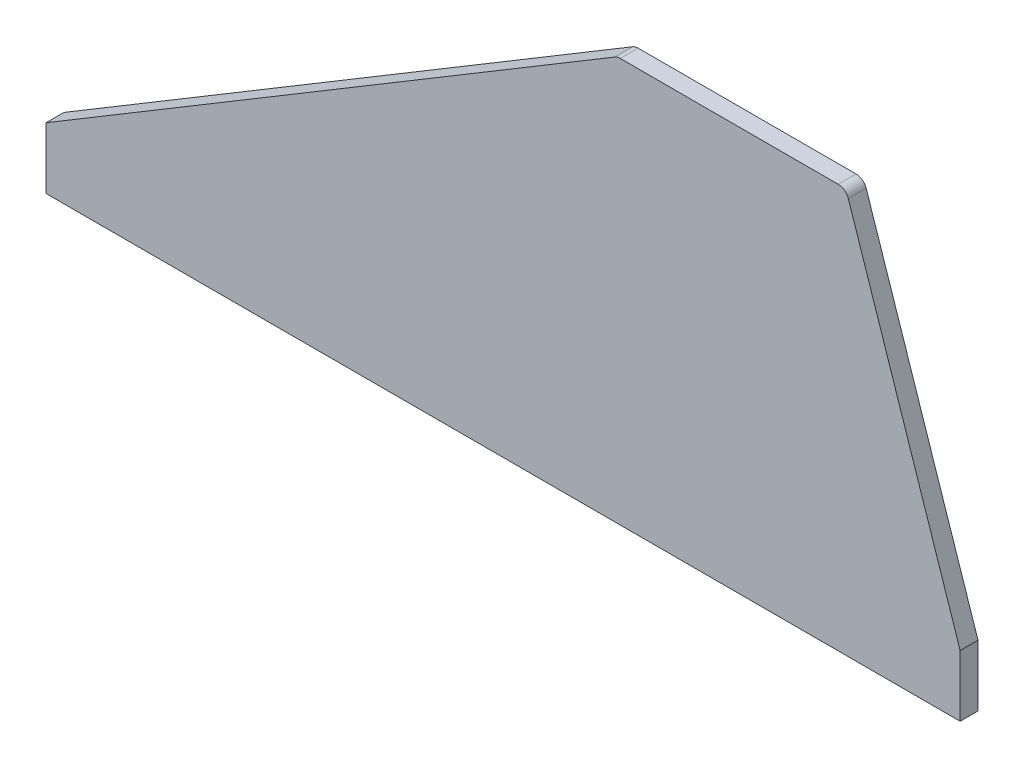
SolidWorks part; units mm, degrees
material "E-Glass Fiber"
ref_plane "Front Plane" through (0, 0, 0) normal (0, 0, 1) x (1, 0, 0)
ref_plane "Top Plane" through (0, 0, 0) normal (0, 1, 0) x (1, 0, 0)
ref_plane "Right Plane" through (0, 0, 0) normal (1, 0, 0) x (0, 0, -1)
sketch "Fin Profile" plane through (0, 0, 0) normal (0, 0, 1) x (1, 0, 0)
  line L0 (406.4, -27.2542) -> (0, -27.2542)
  line L1 (0, -27.2542) -> (0, 0)
  line L2 (0, 0) -> (254, 152.4)
  line L3 (254, 152.4) -> (355.6, 152.4)
  line L5 (355.6, 152.4) -> (406.4, 0)
  line L6 (406.4, 0) -> (406.4, -27.2542)
  dimension "D1" = 27.2542
  dimension "D2" = 406.4
  dimension "D3" = 101.6
  dimension "D4" = 254
  dimension "D5" = 152.4
extrude "Fin Body" add sketch "Fin Profile" along normal blind 7.9375 contours L2 L3 L5 L6 L0 L1
fillet "Fin Fillets" radius 4.7625 2 edges at (355.6, 152.4, 3.9688) (254, 152.4, 3.9688)
equation "\"Root Chord\" = 16"
equation "\"Span\" = 6"
equation "\"Tip Chord\" = 4"
equation "\"Sweep Distance\"= 10"
equation "\"Fin Thickness\" = 5 / 16"
equation "\"Tab Height\"= 1"
equation "\"D1@Fin Profile\"=\"Tab Height\" + (0.17/2) - (0.012)"
equation "\"D2@Fin Profile\" = \"Root Chord\""
equation "\"D3@Fin Profile\" = \"Tip Chord\""
equation "\"D4@Fin Profile\" = \"Sweep Distance\""
equation "\"D5@Fin Profile\" = \"Span\""
equation "\"Fillet Radius\"=0.1875"
equation "\"D1@Fin Fillets\" = \"Fillet Radius\""
equation "\"D1@Fin Body\"=\"Fin Thickness\""
